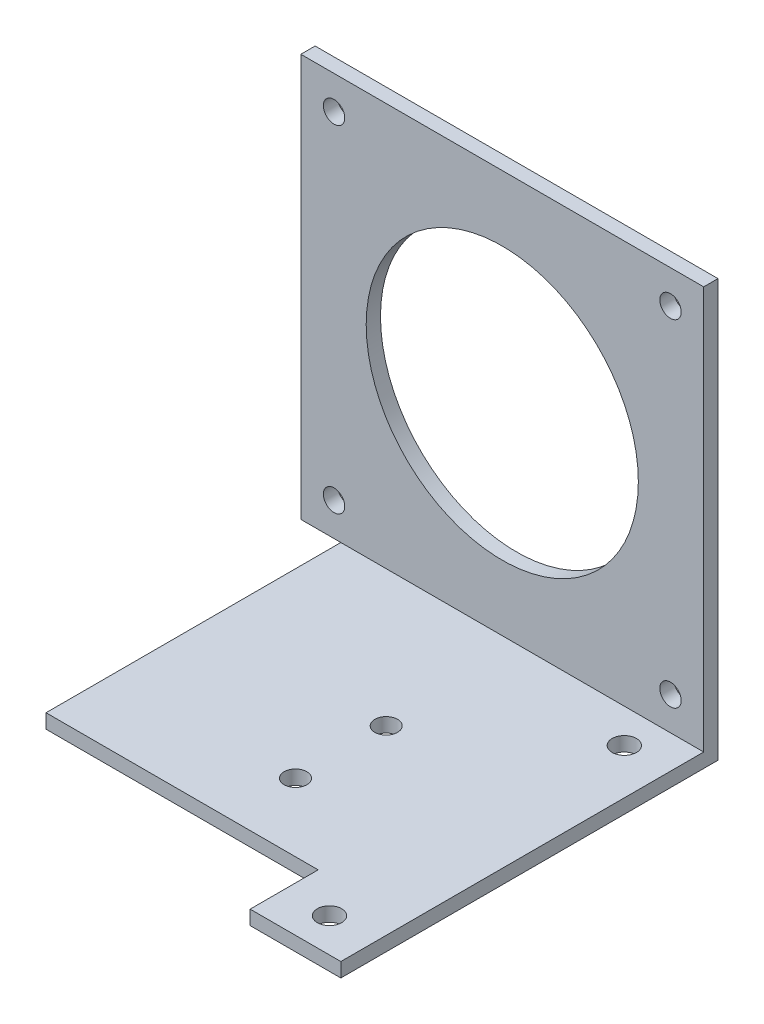
SolidWorks part; units mm, degrees
ref_plane "Front Plane" through (0, 0, 0) normal (0, 0, 1) x (1, 0, 0)
ref_plane "Top Plane" through (0, 0, 0) normal (0, 1, 0) x (1, 0, 0)
ref_plane "Right Plane" through (0, 0, 0) normal (1, 0, 0) x (0, 0, -1)
sketch "Sketch1" plane through (0, 0, 0) normal (0, 1, 0) x (1, 0, 0)
  line L2 (-25.4, 27.4) -> (25.4, 27.4)
  line L3 (25.4, 27.4) -> (25.4, -25.4)
  line L4 (25.4, -25.4) -> (12.7, -25.4)
  line L5 (12.7, -25.4) -> (12.7, -15.875)
  line L6 (12.7, -15.875) -> (-25.4, -15.875)
  line L7 (-25.4, -15.875) -> (-25.4, 27.4)
  line L8 (19.05, 20.6375) -> (19.05, -20.6375) construction
  line L9 (0, 6.35) -> (0, -6.35) construction
  circle A0 centre (19.05, 20.6375) radius 1.7
  circle A1 centre (19.05, -20.6375) radius 1.7
  circle A2 centre (0, 6.35) radius 1.5875
  circle A3 centre (0, -6.35) radius 1.5875
  point P18 (0, 0)
  dimension "D5" = 3.4
  dimension "D9" = 3.175
  dimension "D1" = 50.8
  dimension "D2" = 52.8
  dimension "D3" = 12.7
  dimension "D4" = 9.525
  dimension "D6" = 41.275
  dimension "D7" = 6.35
  dimension "D8" = 25.4
  dimension "D10" = 12.7
  dimension "D11" = 9.525
  dimension "D12" = 4.7625
extrude "Boss-Extrude1" add sketch "Sketch1" along normal blind 2
sketch "Sketch2" plane through (0, 2, 0) normal (0, 1, 0) x (1, 0, 0)
  line L0 (25.4, 27.4) -> (25.4, 25.4)
  line L2 (25.4, -25.4) -> (25.4, 27.4) construction
  line L3 (25.4, 25.4) -> (-31, 25.4)
  line L5 (-31, 25.4) -> (-31, 27.4)
  line L6 (-31, 27.4) -> (25.4, 27.4)
  dimension "D1" = 56.4
  dimension "D2" = 2
extrude "Boss-Extrude2" add sketch "Sketch2" along normal blind 56.4
sketch "Sketch3" plane through (0, 0, -27.4) normal (0, 0, -1) x (-1, 0, 0)
  line L0 (-25.4, 58.4) -> (31, 2) construction
  line L1 (31, 58.4) -> (-25.4, 2) construction
  line L2 (-25.4, 58.4) -> (-25.4, 0) construction
  circle A0 centre (2.8, 30.2) radius 19.05
  circle A1 centre (26.35, 53.75) radius 1.5
  circle A2 centre (26.35, 6.65) radius 1.5
  circle A3 centre (-20.75, 6.65) radius 1.5
  circle A4 centre (-20.75, 53.75) radius 1.5
  dimension "D1" = 3
  dimension "D3" = 38.1
  dimension "D2" = 47.1
extrude "Cut-Extrude1" cut sketch "Sketch3" against normal through all
